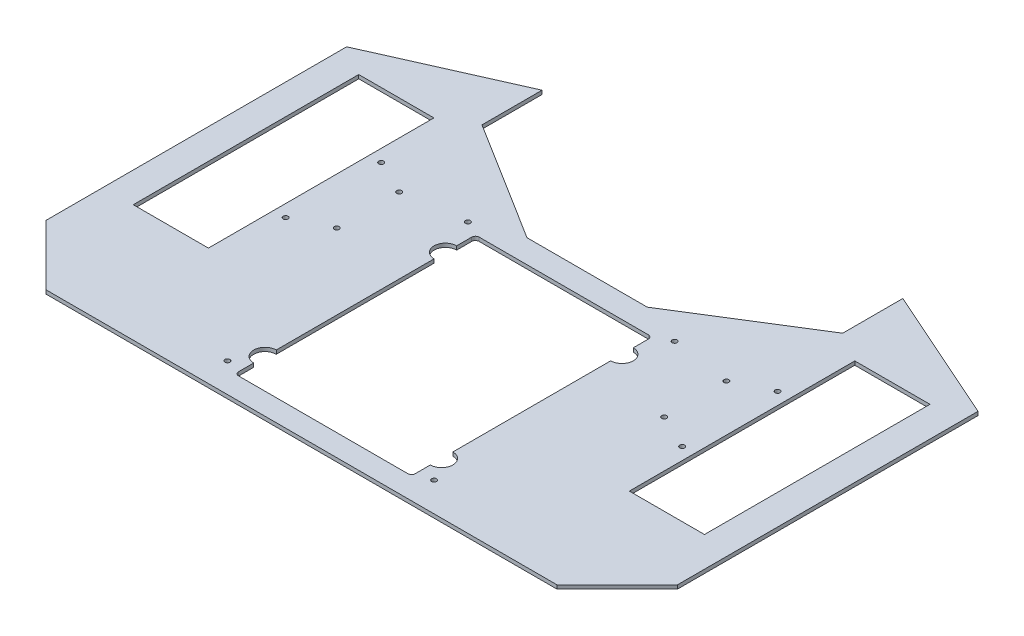
SolidWorks part; units mm, degrees
ref_plane "Front Plane" through (0, 0, 0) normal (0, 0, 1) x (1, 0, 0)
ref_plane "Top Plane" through (0, 0, 0) normal (0, 1, 0) x (1, 0, 0)
ref_plane "Right Plane" through (0, 0, 0) normal (1, 0, 0) x (0, 0, -1)
sketch "Sketch1" plane through (0, 0, 0) normal (0, 1, 0) x (1, 0, 0)
  line L17 (265.3132, -148.5502) -> (201.8132, -148.5502) construction
  line L18 (265.3132, -148.5502) -> (265.3132, -339.0502) construction
  line L19 (265.3132, -339.0502) -> (201.8132, -339.0502) construction
  line L20 (201.8132, -148.5502) -> (201.8132, -339.0502) construction
  line L21 (-153.7868, -148.5502) -> (-153.7868, -339.0502) construction
  line L22 (-217.2868, -339.0502) -> (-153.7868, -339.0502) construction
  line L23 (-217.2868, -148.5502) -> (-217.2868, -339.0502) construction
  line L24 (-217.2868, -148.5502) -> (-153.7868, -148.5502) construction
  line L25 (-242.6868, -133.4325) -> (-242.6868, -385.4912) construction
  line L26 (-191.8868, -438.1717) -> (-242.6868, -387.3717) construction
  line L27 (-191.8868, -438.1717) -> (239.9132, -438.1717) construction
  line L28 (239.9132, -438.1717) -> (290.7132, -387.3717) construction
  line L29 (290.7132, -387.3717) -> (290.7132, -133.3717) construction
  line L30 (290.7132, -133.3717) -> (176.4132, -82.5717) construction
  line L31 (176.4132, -82.5717) -> (176.4132, -133.3717) construction
  line L32 (176.4132, -133.3717) -> (74.8132, -196.8717) construction
  line L33 (74.8132, -196.8717) -> (-26.7868, -196.8717) construction
  line L34 (-128.3868, -133.3717) -> (-26.7868, -196.8717) construction
  line L35 (-128.3868, -82.5717) -> (-128.3868, -133.3717) construction
  line L36 (-242.6868, -133.3717) -> (-128.3868, -82.5717) construction
  line L37 (265.3132, -148.5502) -> (201.8132, -148.5502)
  line L38 (265.3132, -148.5502) -> (265.3132, -339.0502)
  line L39 (265.3132, -339.0502) -> (201.8132, -339.0502)
  line L40 (201.8132, -148.5502) -> (201.8132, -339.0502)
  line L41 (-153.7868, -148.5502) -> (-153.7868, -339.0502)
  line L42 (-217.2868, -339.0502) -> (-153.7868, -339.0502)
  line L43 (-217.2868, -148.5502) -> (-217.2868, -339.0502)
  line L44 (-217.2868, -148.5502) -> (-153.7868, -148.5502)
  line L45 (-242.6868, -133.4325) -> (-242.6868, -385.4912)
  line L46 (-191.8868, -438.1717) -> (-242.6868, -387.3717)
  line L47 (-191.8868, -438.1717) -> (239.9132, -438.1717)
  line L48 (239.9132, -438.1717) -> (290.7132, -387.3717)
  line L49 (290.7132, -387.3717) -> (290.7132, -133.3717)
  line L50 (290.7132, -133.3717) -> (176.4132, -82.5717)
  line L51 (176.4132, -82.5717) -> (176.4132, -133.3717)
  line L52 (176.4132, -133.3717) -> (74.8132, -196.8717)
  line L53 (74.8132, -196.8717) -> (-26.7868, -196.8717)
  line L54 (-128.3868, -133.3717) -> (-26.7868, -196.8717)
  line L55 (-128.3868, -82.5717) -> (-128.3868, -133.3717)
  line L56 (-242.6868, -133.3717) -> (-128.3868, -82.5717)
  line L57 (-242.6868, -133.4325) -> (-242.6868, -133.3717)
  line L58 (-242.6868, -385.4912) -> (-242.6868, -387.3717)
extrude "Boss-Extrude1" add sketch "Sketch1" along normal blind 3.175
sketch "Sketch3" plane through (0, 0, 0) normal (0, 1, 0) x (1, 0, 0)
  line L1 (-143.449, -203.465) -> (-143.449, -284.1354) construction
  line L2 (-143.449, -243.8002) -> (24.0132, -243.8002) construction
  line L3 (-191.8868, -438.1717) -> (239.9132, -438.1717) construction
  line L4 (-217.2868, -339.0502) -> (-153.7868, -339.0502) construction
  point P4 (63.3633, -274.6852)
  point P7 (24.0132, -438.1717)
  line B0 (24.0132, -13.4981) -> (24.0132, 49986.5019) construction
  circle B1 centre (-114.2782, -270.1255) radius 2.0828
  circle B2 centre (-143.449, -284.1354) radius 2.0828
  circle B3 centre (-114.2782, -217.4749) radius 2.0828
  circle B4 centre (-143.449, -203.465) radius 2.0828
  circle B5 centre (191.4754, -284.1354) radius 2.0828
  circle B6 centre (162.3046, -270.1255) radius 2.0828
  circle B7 centre (162.3046, -217.4749) radius 2.0828
  circle B8 centre (191.4754, -203.465) radius 2.0828
  dimension "D1" = 95.25
sketch_block_instance "motor_mount_pattern-1"
sketch_block "motor_mount_pattern"
extrude "Cut-Extrude2" cut sketch "Sketch3" along normal through all
sketch "Sketch4" plane through (0, 0, 0) normal (0, 1, 0) x (1, 0, 0)
  line L0 (24.0132, -54.7802) -> (24.0132, -50054.7802) construction
  line L1 (24.0132, -200460.6227) -> (24.0132, 249539.3773) construction
  circle A0 centre (111.3257, -210.2986) radius 2.0828
  circle A1 centre (111.3257, -413.4986) radius 2.0828
  circle A2 centre (-63.2993, -413.4986) radius 2.0828
  circle A3 centre (-63.2993, -210.2986) radius 2.0828
  line B0 (-50.5993, -216.6486) -> (98.6257, -216.6486)
  line B1 (-50.5993, -216.6486) -> (-50.5993, -232.5236)
  line B2 (-50.5993, -419.8486) -> (98.6257, -419.8486)
  line B3 (98.6257, -216.6486) -> (98.6257, -232.5236)
  line B4 (-50.5993, -251.5736) -> (-50.5993, -384.9236)
  line B5 (98.6257, -251.5736) -> (98.6257, -384.9236)
  line B6 (-50.5993, -403.9736) -> (-50.5993, -419.8486)
  line B7 (98.6257, -403.9736) -> (98.6257, -419.8486)
  arc B8 (-50.5993, -232.5236) -> (-50.5993, -251.5736) centre (-50.5993, -242.0486) ccw
  arc B9 (98.6257, -251.5736) -> (98.6257, -232.5236) centre (98.6257, -242.0486) ccw
  arc B10 (-50.5993, -384.9236) -> (-50.5993, -403.9736) centre (-50.5993, -394.4486) ccw
  arc B11 (98.6257, -403.9736) -> (98.6257, -384.9236) centre (98.6257, -394.4486) ccw
  dimension "D5" = 4.1656
  dimension "D1" = 12.7
  dimension "D2" = 6.35
  dimension "D3" = 12.7
  dimension "D4" = 6.35
sketch_block_instance "electronics_cutout-1"
sketch_block "electronics_cutout" parameters "D4"=17.1095, "D6"=25.5924, "D1"=203.2, "D2"=149.225, "D3"=35.6511, "D5"=24.7946
extrude "Cut-Extrude4" cut sketch "Sketch4" along normal through all
fillet "Fillet2" radius 3.175 4 edges at (-50.5993, 1.5875, 419.8486) (98.6257, 1.5875, 419.8486) (98.6257, 1.5875, 216.6486) (-50.5993, 1.5875, 216.6486)
